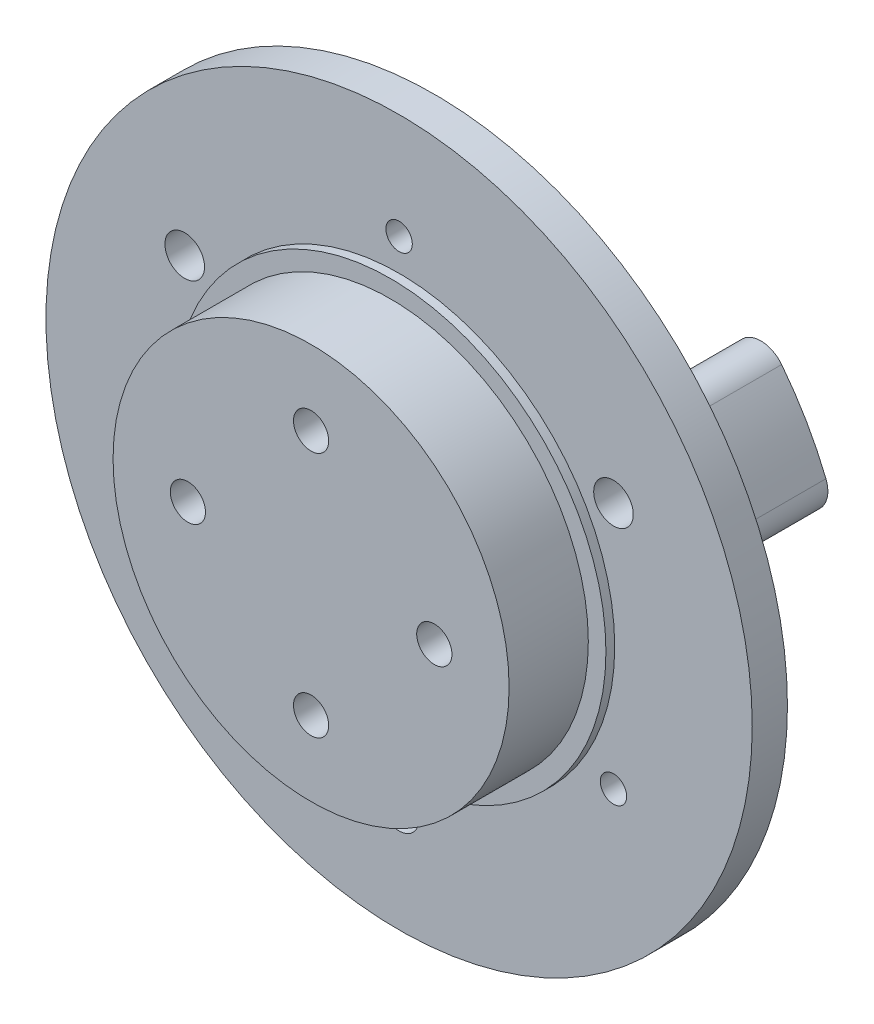
SolidWorks part; units mm, degrees
material "PLA"
ref_plane "Front Plane" through (0, 0, 0) normal (0, 0, 1) x (1, 0, 0)
ref_plane "Top Plane" through (0, 0, 0) normal (0, 1, 0) x (1, 0, 0)
ref_plane "Right Plane" through (0, 0, 0) normal (1, 0, 0) x (0, 0, -1)
sketch "Sketch1" plane through (0, 0, 0) normal (0, 0, 1) x (1, 0, 0)
  circle A0 centre (0, 0) radius 28.125 construction
  circle A1 centre (0, 28.125) radius 6
  circle A2 centre (24.357, -14.0625) radius 6
  circle A3 centre (-24.357, -14.0625) radius 6
  circle A4 centre (0, 0) radius 40.125
  point P11 (0, 0)
  dimension "D1" = 56.25
  dimension "D2" = 12
  dimension "D4" = 12
  dimension "D3" = 3
extrude "Boss-Extrude1" add sketch "Sketch1" along normal blind 4 contours A4 A1 A2 A3 | A1 | A3 | A2 region at (0, 28.125, 0) region at (24.357, -14.0625, 0) region at (-24.357, -14.0625, 0) region at (0, 0, 0)
extrude "Boss-Extrude2" add sketch "Sketch1<3>" against normal blind 4.8 contours A1 | A2 | A3 region at (0, 28.125, 0) region at (24.357, -14.0625, 0) region at (-24.357, -14.0625, 0)
sketch "Sketch1<3>" plane through (0, 0, 0) normal (0, 0, 1) x (1, 0, 0) same geometry as "Sketch1"
sketch "Sketch2" plane through (0, 0, 0) normal (0, 0, -1) x (-1, 0, 0)
  circle A0 centre (24.357, -14.0625) radius 6 construction
  circle A1 centre (-24.357, -14.0625) radius 6 construction
  circle A2 centre (0, 28.125) radius 6 construction
  circle A3 centre (24.357, -14.0625) radius 6
  circle A4 centre (-24.357, -14.0625) radius 6
  circle A5 centre (0, 28.125) radius 6
  circle A6 centre (0, 28.125) radius 7
  circle A7 centre (-24.357, -14.0625) radius 7
  circle A8 centre (24.357, -14.0625) radius 7
  dimension "D1" = 1
extrude "Boss-Extrude3" add sketch "Sketch2" along normal blind 1
sketch "Sketch3" plane through (0, 0, 4) normal (0, 0, 1) x (1, 0, 0)
  circle A0 centre (0, 0) radius 22.5
  circle A1 centre (0, 0) radius 24.5
  dimension "D1" = 45
  dimension "D2" = 2
extrude "Boss-Extrude4" add sketch "Sketch3" along normal blind 10 contours A0 region at (0, 0, 4)
extrude "Boss-Extrude5" add sketch "Sketch3<3>" along normal blind 1
sketch "Sketch3<3>" plane through (0, 0, 4) normal (0, 0, 1) x (1, 0, 0) same geometry as "Sketch3"
sketch "Sketch4" plane through (0, 0, 14) normal (0, 0, 1) x (1, 0, 0)
  line L0 (0, 0) -> (0, 14) construction
  circle A0 centre (0, 0) radius 14 construction
  circle A1 centre (0, 14) radius 2
  circle A2 centre (14, 0) radius 2
  circle A3 centre (0, -14) radius 2
  circle A4 centre (-14, 0) radius 2
  dimension "D1" = 28
  dimension "D2" = 4
  dimension "D4" = 14
  dimension "D3" = 4
extrude "Cut-Extrude1" cut sketch "Sketch4" against normal through all
sketch "Sketch5" plane through (0, 0, -4.8) normal (0, 0, -1) x (-1, 0, 0)
  line L0 (0, 0) -> (0, 28.125) construction
  circle A0 centre (0, 28.125) radius 1.5
  circle A1 centre (24.357, -14.0625) radius 1.5
  circle A2 centre (-24.357, -14.0625) radius 1.5
  dimension "D1" = 3
  dimension "D3" = 28.125
  dimension "D2" = 3
extrude "Cut-Extrude2" cut sketch "Sketch5" against normal through all
sketch "Sketch6" plane through (0, 0, 4) normal (0, 0, 1) x (1, 0, 0)
  circle A0 centre (0, 28.125) radius 2.25
  circle M2 centre (0, 28.125) radius 1.5
  dimension "D1" = 4.5
extrude "Cut-Extrude3" cut sketch "Sketch6" against normal blind 5
sketch "Sketch7" plane through (0, 0, 0) normal (0, 0, -1) x (-1, 0, 0)
  circle A0 centre (0, 14) radius 2.8
  dimension "D1" = 5.6
extrude "Cut-Extrude4" cut sketch "Sketch7" against normal blind 5
pattern_circular "CirPattern2" count 4 over 360 about axis through (0, 0, 0) along (0, 0, 1) of "Cut-Extrude4"
sketch "Sketch8" plane through (0, 0, 0) normal (0, 0, -1) x (-1, 0, 0)
  line L0 (0, 0) -> (-24.357, 14.0625) construction
  line L1 (0, 0) -> (0, 28.125) construction
  line L4 (0, 0) -> (-25.68, 30.831) construction
  line L5 (-26.0513, 25.0269) -> (-15.6965, 12.595)
  line L6 (-34.6996, 10.0477) -> (-18.7559, 7.2961)
  line L7 (0, 0) -> (-31.1296, 5.3724) construction
  circle A7 centre (0, 28.125) radius 18 construction
  circle A8 centre (24.357, -14.0625) radius 18 construction
  circle A9 centre (-24.357, -14.0625) radius 18 construction
  circle A10 centre (0, 0) radius 40.125 construction
  arc A11 (-18.7559, 7.2961) -> (-15.6965, 12.595) centre (0, 0) cw
  arc A12 (-34.6996, 10.0477) -> (-26.0513, 25.0269) centre (0, 0) cw
  circle A13 centre (-24.357, 14.0625) radius 1.5
  circle A14 centre (0, 0) radius 28.125 construction
  point P8 (0, 0)
  point P18 (0, 0)
  dimension "D1" = 36
  dimension "D3" = 4
  dimension "D4" = 3
  dimension "D5" = 8
  dimension "D6" = 8
  dimension "D2" = 3
  dimension "D7" = 60
extrude "Boss-Extrude6" add sketch "Sketch8" along normal blind 11
fillet "Fillet1" radius 3 4 edges at (26.0513, 25.0269, -5.5) (34.6996, 10.0477, -5.5) (15.6965, 12.595, -5.5) (18.7559, 7.2961, -5.5)
extrude "Cut-Extrude5" cut sketch "Sketch8<2>" against normal through all contours A13 region at (24.357, 14.0625, 0)
sketch "Sketch8<2>" plane through (0, 0, 0) normal (0, 0, -1) x (-1, 0, 0) same geometry as "Sketch8"
pattern_circular "CirPattern3" count 3 over 360 about axis through (0, 0, 4) along (0, 0, 1) of "Boss-Extrude6", "Fillet1", "Cut-Extrude5"
pattern_circular "CirPattern1" count 6 over 360 about axis through (0, 0, 4) along (0, 0, 1) skipping 2, 4 of "Cut-Extrude3"
extrude "Boss-Extrude7" add sketch "Sketch6<2>" against normal up to surface (5 mm away) contours A0 M2 region at (-2.1864, 28.125, 4) up to face at (2.25, 28.125, -1)
sketch "Sketch6<2>" plane through (0, 0, 4) normal (0, 0, 1) x (1, 0, 0) same geometry as "Sketch6"
